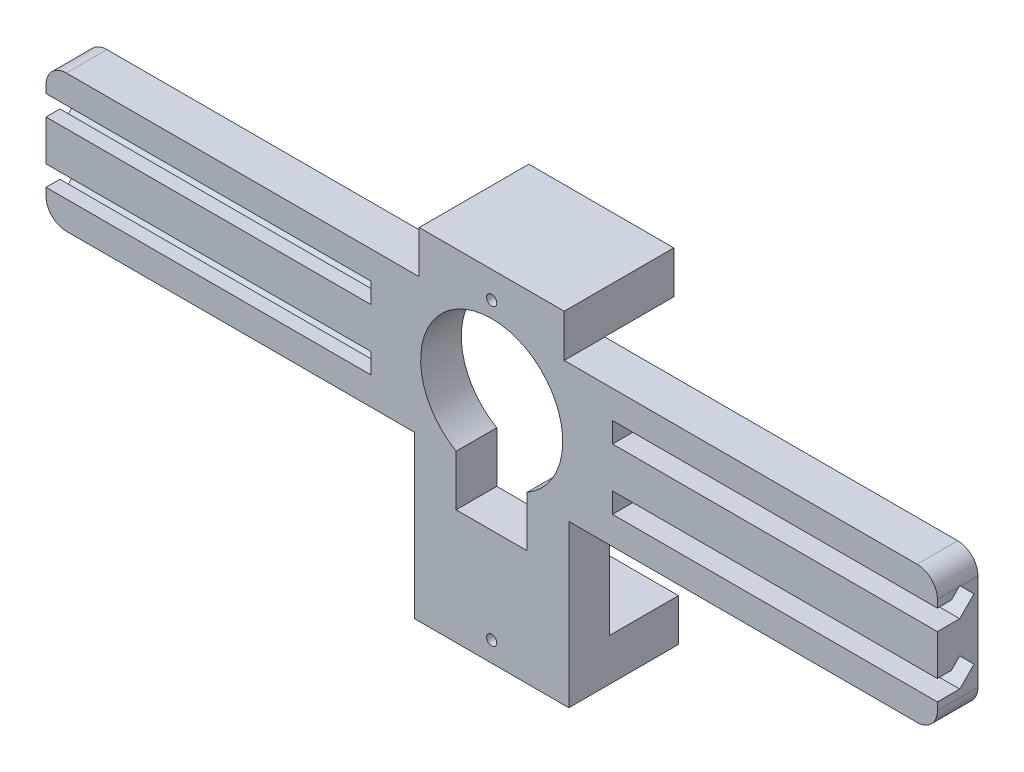
SolidWorks part; units mm, degrees
ref_plane "前视基准面" through (0, 0, 0) normal (0, 0, 1) x (1, 0, 0)
ref_plane "上视基准面" through (0, 0, 0) normal (0, 1, 0) x (1, 0, 0)
ref_plane "右视基准面" through (0, 0, 0) normal (1, 0, 0) x (0, 0, -1)
sketch "草图1" plane through (0, 0, 0) normal (0, 0, 1) x (1, 0, 0)
  line L0 (0, 19.8094) -> (0, -25.2091) construction
  line L1 (7.1414, 7) -> (43.9, 7)
  line L2 (-3.5, -11.0622) -> (3.5, -11.0622)
  line L3 (-3.5, -11.0622) -> (-3.5, -6.0622)
  line L4 (11.9, 2) -> (43.9, 2) construction
  line L5 (3.5, -11.0622) -> (3.5, -6.0622)
  line L6 (-3.5, -11.0622) -> (3.5, -6.0622) construction
  line L7 (-3.5, -6.0622) -> (3.5, -11.0622) construction
  line L8 (11.9, 2) -> (11.9, 4) construction
  line L9 (11.9, 4) -> (43.9, 4) construction
  line L10 (43.9, 2) -> (43.9, 4) construction
  line L11 (11.9, -2) -> (43.9, -2) construction
  line L12 (11.9, -2) -> (11.9, -4) construction
  line L13 (11.9, -4) -> (43.9, -4) construction
  line L14 (43.9, -2) -> (43.9, -4) construction
  line L15 (43.9, 7) -> (43.9, -6.5)
  line L16 (43.9, -6.5) -> (7.5993, -6.5)
  line L17 (7.1414, 7) -> (7.1414, 11.2)
  line L18 (7.1414, 11.2) -> (-7.1414, 11.2)
  line L19 (7.5993, -6.5) -> (7.5993, -22.4)
  line L20 (7.5993, -22.4) -> (-7.5993, -22.4)
  line L21 (-43.9, -2) -> (-43.9, -4) construction
  line L22 (-43.9, 2) -> (-43.9, 4) construction
  line L23 (-11.9, 2) -> (-11.9, 4) construction
  line L24 (-11.9, 4) -> (-43.9, 4) construction
  line L25 (-11.9, 2) -> (-43.9, 2) construction
  line L26 (-43.9, 7) -> (-43.9, -6.5)
  line L27 (-11.9, -2) -> (-11.9, -4) construction
  line L28 (-11.9, -2) -> (-43.9, -2) construction
  line L29 (-11.9, -4) -> (-43.9, -4) construction
  line L30 (-7.5993, -6.5) -> (-7.5993, -22.4)
  line L31 (-43.9, -6.5) -> (-7.5993, -6.5)
  line L32 (-7.1414, 7) -> (-43.9, 7)
  line L33 (-7.1414, 7) -> (-7.1414, 11.2)
  arc A0 (3.5, -6.0622) -> (-3.5, -6.0622) centre (0, 0) ccw
  circle A1 centre (0, 8.575) radius 0.5
  circle A2 centre (0, -20.42) radius 0.5
  circle A3 centre (0, 0) radius 10 construction
  point P9 (0, -8.5622)
  point P27 (43.9, -3)
  point P42 (0, -22.4)
  point P45 (0, 11.2)
  dimension "D1" = 14
  dimension "D2" = 1
  dimension "D3" = 1
  dimension "D4" = 8.575
  dimension "D21" = 20
  dimension "D5" = 20.42
  dimension "D6" = 5
  dimension "D7" = 7
  dimension "D8" = 2
  dimension "D9" = 2
  dimension "D10" = 4
  dimension "D11" = 2
  dimension "D12" = 11.9
  dimension "D13" = 11.9
  dimension "D14" = 32
  dimension "D15" = 32
  dimension "D16" = 11.2
  dimension "D17" = 3
  dimension "D18" = 2.5
  dimension "D19" = 22.4
  dimension "D20" = 0
extrude "凸台-拉伸1" add sketch "草图1" along normal blind 4
sketch "草图2" plane through (43.9, 0, 0) normal (1, 0, 0) x (0, 0, -1)
  line L0 (-4, -6.5) -> (-4, 7) construction
  line L1 (-4, 2.25) -> (-1.8, 2.25)
  line L2 (-4, 2.25) -> (-4, 4.25)
  line L3 (-4, 4.25) -> (-2.6284, 4.25)
  line L4 (-1.8, -3.75) -> (-0.3858, -2.3358)
  line L5 (-1.8, 2.25) -> (-0.3858, 3.6642)
  line L6 (-0.3858, 3.6642) -> (-1.8, 5.0784)
  line L7 (-1.8, 5.0784) -> (-2.6284, 4.25)
  line L8 (-4, -1.75) -> (-2.6284, -1.75)
  line L9 (-4, -1.75) -> (-4, -3.75)
  line L10 (-4, -3.75) -> (-1.8, -3.75)
  line L12 (-0.3858, -2.3358) -> (-1.8, -0.9216)
  line L13 (-1.8, -0.9216) -> (-2.6284, -1.75)
  point P6 (-4, 0.25)
  dimension "D1" = 2
  dimension "D2" = 2.2
  dimension "D3" = 135
  dimension "D4" = 2
  dimension "D5" = 90
  dimension "D6" = 2
  dimension "D7" = 90
  dimension "D8" = 2
  dimension "D9" = 2
  dimension "D10" = 2
  dimension "D11" = 2.2
  dimension "D12" = 135
  dimension "D13" = 2
  dimension "D14" = 2
extrude "切除-拉伸1" cut sketch "草图2" against normal blind 32
mirror "镜向1" about plane through (0, 0, 0) normal (1, 0, 0) of "切除-拉伸1"
fillet "圆角2" radius 2 4 edges at (-43.9, -6.5, 2) (-43.9, 7, 2) (43.9, 7, 2) (43.9, -6.5, 2)
sketch "草图3" plane through (0, 0, 0) normal (0, 0, -1) x (-1, 0, 0)
  line L0 (7.1414, 11.2) -> (7.1414, 7) construction
  line L1 (-7.1414, 11.2) -> (7.1414, 11.2)
  line L2 (-7.1414, 11.2) -> (-7.1414, 7.03)
  line L3 (-7.1414, 7.03) -> (7.1414, 7.03)
  line L4 (7.1414, 11.2) -> (7.1414, 7.03)
  line L5 (-7.5993, -22.4) -> (-7.5993, -6.5) construction
  line L6 (7.5993, -22.4) -> (-7.5993, -22.4)
  line L7 (7.5993, -22.4) -> (7.5993, -18.23)
  line L8 (7.5993, -18.23) -> (-7.5993, -18.23)
  line L9 (-7.5993, -22.4) -> (-7.5993, -18.23)
  circle A0 centre (0, 8.575) radius 0.5
  circle A1 centre (0, -20.42) radius 0.5
  dimension "D3" = 1
  dimension "D4" = 1
  dimension "D1" = 4.17
  dimension "D2" = 4.17
extrude "凸台-拉伸2" add sketch "草图3" along normal blind 6.8
sketch "Croquis1" plane through (-43.9, 0, 0) normal (-1, 0, 0) x (0, 0, 1)
  line L0 (0, 5) -> (4, 5)
  line L1 (0, 5) -> (0, -4.5)
  line L2 (4, 5) -> (4, -4.5)
  line L3 (0, -4.5) -> (4, -4.5)
  line L13 (0, 5) -> (0, -4.5)
  line L14 (0, -4.5) -> (4, -4.5)
  line L15 (4, -4.5) -> (4, -3.75)
  line L16 (4, -3.75) -> (1.8, -3.75)
  line L17 (1.8, -3.75) -> (0.3858, -2.3358)
  line L18 (0.3858, -2.3358) -> (1.8, -0.9216)
  line L19 (1.8, -0.9216) -> (2.6284, -1.75)
  line L20 (2.6284, -1.75) -> (4, -1.75)
  line L21 (4, -1.75) -> (4, 2.25)
  line L22 (4, 2.25) -> (1.8, 2.25)
  line L23 (1.8, 2.25) -> (0.3858, 3.6642)
  line L24 (0.3858, 3.6642) -> (1.7216, 5)
  line L25 (1.7216, 5) -> (0, 5)
  line L26 (0, 5) -> (0, -4.5)
  line L27 (0, -4.5) -> (4, -4.5)
  line L28 (4, -4.5) -> (4, -3.75)
  line L29 (4, -3.75) -> (1.8, -3.75)
  line L30 (1.8, -3.75) -> (0.3858, -2.3358)
  line L31 (0.3858, -2.3358) -> (1.8, -0.9216)
  line L32 (1.8, -0.9216) -> (2.6284, -1.75)
  line L33 (2.6284, -1.75) -> (4, -1.75)
  line L34 (4, -1.75) -> (4, 2.25)
  line L35 (4, 2.25) -> (1.8, 2.25)
  line L36 (1.8, 2.25) -> (0.3858, 3.6642)
  line L37 (0.3858, 3.6642) -> (1.7216, 5)
  line L38 (1.7216, 5) -> (0, 5)
  line M14 (0, 5) -> (0, -4.5)
  line M15 (0, -4.5) -> (4, -4.5)
  line M16 (4, -4.5) -> (4, -3.75)
  line M17 (4, -3.75) -> (1.8, -3.75)
  line M18 (1.8, -3.75) -> (0.3858, -2.3358)
  line M19 (0.3858, -2.3358) -> (1.8, -0.9216)
  line M20 (1.8, -0.9216) -> (2.6284, -1.75)
  line M21 (2.6284, -1.75) -> (4, -1.75)
  line M22 (4, -1.75) -> (4, 2.25)
  line M23 (4, 2.25) -> (1.8, 2.25)
  line M24 (1.8, 2.25) -> (0.3858, 3.6642)
  line M25 (0.3858, 3.6642) -> (1.7216, 5)
  line M26 (1.7216, 5) -> (0, 5)
  dimension "D1" = 0
extrude "Saliente-Extruir1" add sketch "Croquis1" along normal up to surface from surface contours M26 M14 M15 M16 M17 M18 M19 M20 M21 M22 M23 M24 M25 | L2 M21 M20 M19 M18 M17 | L2 L0 M25 M24 M23 region at (-43.9, -0.1063, 1.7093) region at (-43.9, 3.6342, 2.5099) region at (-43.9, -2.5622, 2.392) up to face at (-43.9, -0.3918, 2.0401) starting at face at (-11.9, 3.6238, 2.4357)
sketch "Croquis4" plane through (-43.9, 0, 0) normal (-1, 0, 0) x (0, 0, 1)
  line L0 (4, 0.25) -> (0, 0.25) construction
  line L1 (4, -4.5) -> (1.8784, -4.5)
  line L2 (4, -3.75) -> (4, -4.5)
  line L3 (2.6284, -3.75) -> (4, -3.75)
  line L4 (1.8784, 5) -> (2.6284, 4.25)
  line L5 (4, 5) -> (1.8784, 5)
  line L6 (4, 4.25) -> (4, 5)
  line L7 (2.6284, 4.25) -> (4, 4.25)
  line L9 (4, 5) -> (1.8784, 5)
  line L10 (4, 4.25) -> (4, 5)
  line L11 (2.6284, 4.25) -> (4, 4.25)
  line L12 (1.8784, -4.5) -> (2.6284, -3.75)
  line L13 (0, 5) -> (0, -4.5)
  line L14 (1.7216, 5) -> (0, 5)
  line L15 (0.3858, 3.6642) -> (1.7216, 5)
  line L16 (1.8, 2.25) -> (0.3858, 3.6642)
  line L17 (4, 2.25) -> (1.8, 2.25)
  line L18 (4, -1.75) -> (4, 2.25)
  line L19 (2.6284, -1.75) -> (4, -1.75)
  line L20 (1.8, -0.9216) -> (2.6284, -1.75)
  line L21 (0.3858, -2.3358) -> (1.8, -0.9216)
  line L22 (1.8, -3.75) -> (0.3858, -2.3358)
  line L23 (4, -3.75) -> (1.8, -3.75)
  line L24 (4, -4.5) -> (4, -3.75)
  line L25 (0, -4.5) -> (4, -4.5)
  line L26 (0, 5) -> (0, -4.5)
  line L27 (1.7216, 5) -> (0, 5)
  line L30 (4, 2.25) -> (2.6284, 2.25)
  line L31 (4, -1.75) -> (4, 2.25)
  line L32 (2.6284, -1.75) -> (4, -1.75)
  line L36 (4, -3.75) -> (2.6284, -3.75)
  line L37 (4, -4.5) -> (4, -3.75)
  line L38 (0, -4.5) -> (1.7216, -4.5)
  line L39 (1.7216, -4.5) -> (0, -4.5)
  line L40 (0.3858, -3.1642) -> (1.7216, -4.5)
  line L41 (1.8, -1.75) -> (0.3858, -3.1642)
  line L42 (4, -1.75) -> (1.8, -1.75)
  line L43 (2.6284, 2.25) -> (4, 2.25)
  line L44 (1.8, 1.4216) -> (2.6284, 2.25)
  line L45 (0.3858, 2.8358) -> (1.8, 1.4216)
  line L46 (1.8, 4.25) -> (0.3858, 2.8358)
  line L47 (4, 4.25) -> (1.8, 4.25)
  line L48 (4, 5) -> (4, 4.25)
  line L49 (0, 5) -> (4, 5)
  line L50 (4, 4.25) -> (4, 2.25)
  line L51 (4, -1.75) -> (4, -3.75)
  line L52 (1.8784, -4.5) -> (1.8, -4.5784)
  line L54 (1.8, -4.5784) -> (1.7216, -4.5)
  line L55 (1.8, 5.0784) -> (1.7216, 5)
  line L56 (1.7216, 5) -> (1.8784, 5)
  line L57 (1.8784, 5) -> (1.8, 5.0784)
  line L59 (1.7216, 5) -> (1.8784, 5)
  line L61 (1.8784, -4.5) -> (4, -4.5)
  line M20 (0, -4.5) -> (4, -4.5)
  line M21 (4, -4.5) -> (4, 5)
  dimension "D1" = 0
  dimension "D2" = 0
  dimension "D3" = 0
extrude "Cortar-Extruir1" cut sketch "Croquis4" against normal blind 32 contours L11 L47 L46 L45 L44 L30 M21 | L32 L42 L41 L40 L12 L3 M20 M21 | L54 L52 M20 region at (-43.9, -3.689, 1.415) region at (-43.9, -4.5261, 1.8) region at (-43.9, -2.75, 2.6346) region at (-43.9, 3.25, 2.6346) region at (-43.9, 2.3072, 1.4168)
sketch "Croquis7" plane through (0, 0, 4) normal (0, 0, 1) x (1, 0, 0)
  line L28 (-43.9, 5) -> (-43.9, 4.25)
  line L29 (-43.9, 4.25) -> (-11.9, 4.25)
  line L30 (-11.9, 4.25) -> (-11.9, 2.25)
  line L31 (-11.9, 2.25) -> (-43.9, 2.25)
  line L32 (-43.9, 2.25) -> (-43.9, -1.75)
  line L33 (-43.9, -1.75) -> (-11.9, -1.75)
  line L34 (-11.9, -1.75) -> (-11.9, -3.75)
  line L35 (-11.9, -3.75) -> (-43.9, -3.75)
  line L36 (-43.9, -3.75) -> (-43.9, -4.5)
  line L37 (-41.9, -6.5) -> (-7.5993, -6.5)
  line L38 (-7.5993, -6.5) -> (-7.5993, -22.4)
  line L39 (-7.5993, -22.4) -> (7.5993, -22.4)
  line L40 (7.5993, -22.4) -> (7.5993, -6.5)
  line L41 (7.5993, -6.5) -> (41.9, -6.5)
  line L42 (43.9, -4.5) -> (43.9, -3.75)
  line L43 (43.9, -3.75) -> (11.9, -3.75)
  line L44 (11.9, -3.75) -> (11.9, -1.75)
  line L45 (11.9, -1.75) -> (43.9, -1.75)
  line L46 (43.9, -1.75) -> (43.9, 2.25)
  line L47 (43.9, 2.25) -> (11.9, 2.25)
  line L48 (11.9, 2.25) -> (11.9, 4.25)
  line L49 (11.9, 4.25) -> (43.9, 4.25)
  line L50 (43.9, 4.25) -> (43.9, 5)
  line L51 (41.9, 7) -> (7.1414, 7)
  line L52 (7.1414, 7) -> (7.1414, 11.2)
  line L53 (7.1414, 11.2) -> (-7.1414, 11.2)
  line L54 (-7.1414, 11.2) -> (-7.1414, 7)
  line L55 (-7.1414, 7) -> (-41.9, 7)
  line L56 (-43.9, 5) -> (-43.9, 4.25)
  line L57 (-43.9, 4.25) -> (-11.9, 4.25)
  line L58 (-11.9, 4.25) -> (-11.9, 2.25)
  line L59 (-11.9, 2.25) -> (-43.9, 2.25)
  line L60 (-43.9, 2.25) -> (-43.9, -1.75)
  line L61 (-43.9, -1.75) -> (-11.9, -1.75)
  line L62 (-11.9, -1.75) -> (-11.9, -3.75)
  line L63 (-11.9, -3.75) -> (-43.9, -3.75)
  line L64 (-43.9, -3.75) -> (-43.9, -4.5)
  line L65 (-41.9, -6.5) -> (-7.5993, -6.5)
  line L66 (-7.5993, -6.5) -> (-7.5993, -22.4)
  line L67 (-7.5993, -22.4) -> (7.5993, -22.4)
  line L68 (7.5993, -22.4) -> (7.5993, -6.5)
  line L69 (7.5993, -6.5) -> (41.9, -6.5)
  line L70 (43.9, -4.5) -> (43.9, -3.75)
  line L71 (43.9, -3.75) -> (11.9, -3.75)
  line L72 (11.9, -3.75) -> (11.9, -1.75)
  line L73 (11.9, -1.75) -> (43.9, -1.75)
  line L74 (43.9, -1.75) -> (43.9, 2.25)
  line L75 (43.9, 2.25) -> (11.9, 2.25)
  line L76 (11.9, 2.25) -> (11.9, 4.25)
  line L77 (11.9, 4.25) -> (43.9, 4.25)
  line L78 (43.9, 4.25) -> (43.9, 5)
  line L79 (41.9, 7) -> (7.1414, 7)
  line L80 (7.1414, 7) -> (7.1414, 11.2)
  line L81 (7.1414, 11.2) -> (-7.1414, 11.2)
  line L82 (-7.1414, 11.2) -> (-7.1414, 7)
  line L83 (-7.1414, 7) -> (-41.9, 7)
  arc A4 (-43.9, -4.5) -> (-41.9, -6.5) centre (-41.9, -4.5) ccw
  arc A5 (41.9, -6.5) -> (43.9, -4.5) centre (41.9, -4.5) ccw
  arc A6 (43.9, 5) -> (41.9, 7) centre (41.9, 5) ccw
  arc A7 (-41.9, 7) -> (-43.9, 5) centre (-41.9, 5) ccw
  arc A8 (-43.9, -4.5) -> (-41.9, -6.5) centre (-41.9, -4.5) ccw
  arc A9 (41.9, -6.5) -> (43.9, -4.5) centre (41.9, -4.5) ccw
  arc A10 (43.9, 5) -> (41.9, 7) centre (41.9, 5) ccw
  arc A11 (-41.9, 7) -> (-43.9, 5) centre (-41.9, 5) ccw
  dimension "D2" = 43.9
  dimension "D1" = 0
